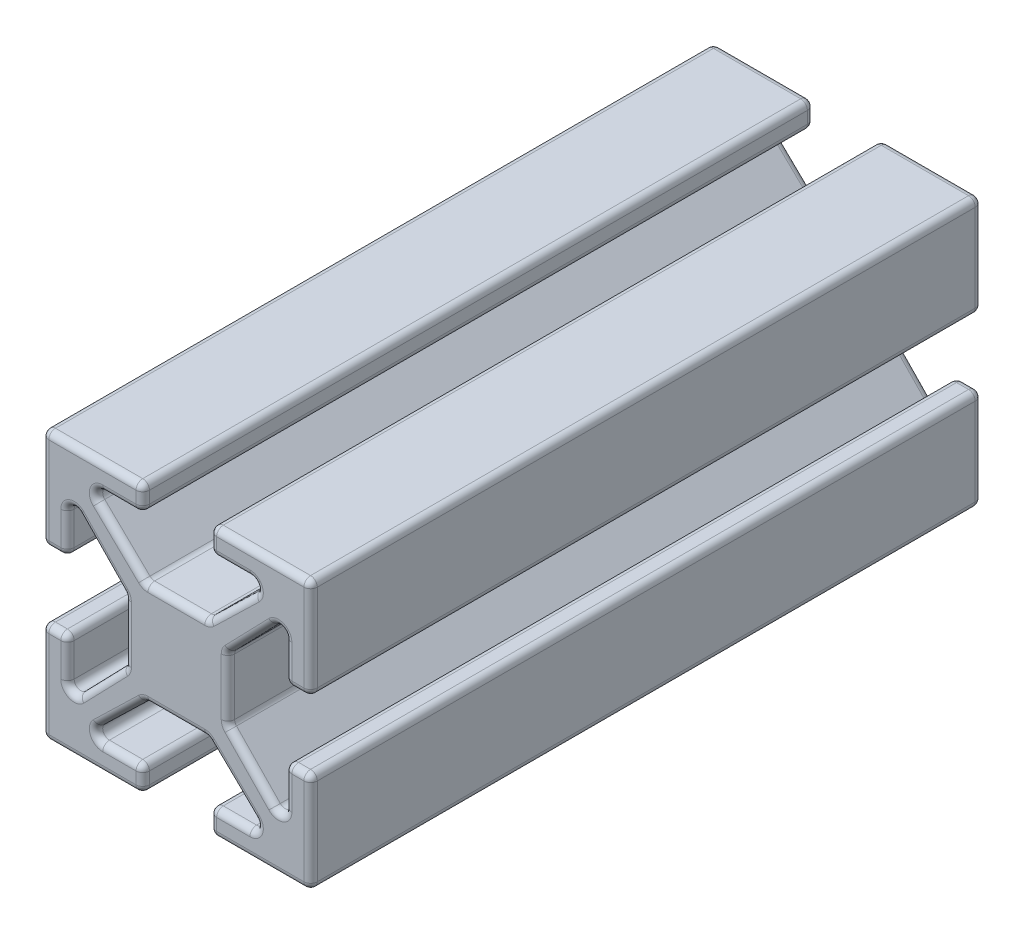
SolidWorks part; units mm, degrees
ref_plane "Front Plane" through (0, 0, 0) normal (0, 0, 1) x (1, 0, 0)
ref_plane "Top Plane" through (0, 0, 0) normal (0, 1, 0) x (1, 0, 0)
ref_plane "Right Plane" through (0, 0, 0) normal (1, 0, 0) x (0, 0, -1)
sketch "Sketch1" plane through (0, 0, 0) normal (0, 0, 1) x (1, 0, 0)
  line L0 (-5, 20) -> (-5, 16.2126)
  line L1 (-20, -20) -> (20, -20)
  line L2 (-20, -20) -> (-20, 20)
  line L3 (-20, 20) -> (20, 20)
  line L4 (20, -20) -> (20, 20)
  line L5 (-20, -20) -> (20, 20) construction
  line L6 (-20, 20) -> (20, -20) construction
  line L7 (-5, 16.2126) -> (-13.4323, 16.2126)
  line L8 (-13.4323, 16.2126) -> (-4.6312, 7.6894)
  line L9 (-4.6312, 7.6894) -> (0, 7.6894)
  line L10 (-7.6894, 4.6312) -> (-7.6894, 0)
  line L11 (-16.2126, 13.4323) -> (-7.6894, 4.6312)
  line L12 (-16.2126, 5) -> (-16.2126, 13.4323)
  line L13 (-20, 5) -> (-16.2126, 5)
  line L14 (0, 7.6894) -> (0, 16.8611) construction
  line L15 (0, 0) -> (-11.384, 0) construction
  line L16 (5, 20) -> (5, 16.2126)
  line L17 (5, 16.2126) -> (13.4323, 16.2126)
  line L18 (13.4323, 16.2126) -> (4.6312, 7.6894)
  line L19 (16.2126, 13.4323) -> (7.6894, 4.6312)
  line L20 (16.2126, 5) -> (16.2126, 13.4323)
  line L21 (20, 5) -> (16.2126, 5)
  line L22 (7.6894, 4.6312) -> (7.6894, 0)
  line L23 (4.6312, 7.6894) -> (0, 7.6894)
  line L24 (20, -5) -> (16.2126, -5)
  line L25 (16.2126, -5) -> (16.2126, -13.4323)
  line L26 (16.2126, -13.4323) -> (7.6894, -4.6312)
  line L27 (13.4323, -16.2126) -> (4.6312, -7.6894)
  line L28 (5, -16.2126) -> (13.4323, -16.2126)
  line L29 (5, -20) -> (5, -16.2126)
  line L30 (4.6312, -7.6894) -> (0, -7.6894)
  line L31 (7.6894, -4.6312) -> (7.6894, 0)
  line L32 (-5, -20) -> (-5, -16.2126)
  line L33 (-5, -16.2126) -> (-13.4323, -16.2126)
  line L34 (-13.4323, -16.2126) -> (-4.6312, -7.6894)
  line L35 (-16.2126, -13.4323) -> (-7.6894, -4.6312)
  line L36 (-16.2126, -5) -> (-16.2126, -13.4323)
  line L37 (-20, -5) -> (-16.2126, -5)
  line L38 (-7.6894, -4.6312) -> (-7.6894, 0)
  line L39 (-4.6312, -7.6894) -> (0, -7.6894)
  point P0 (0, 0)
  point P52 (0, 0)
  dimension "D1" = 40
  dimension "D2" = 40
  dimension "D4" = 15
  dimension "D3" = 4
extrude "Boss-Extrude1" add sketch "Sketch1" along normal blind 100 contours L34 L39 L30 L27 L28 L29 L1 L4 L24 L25 L26 L31 L22 L19 L20 L21 L3 L16 L17 L18 L23 L9 L8 L7 L0 L2 L13 L12 L11 L10 L38 L35 L36 L37 L32 L33 region at (0, 0, 0)
fillet "Fillet3" radius 1 108 edges at (-9.0317, -11.951, 0) (0, -7.6894, 0) (9.0317, -11.951, 0) (9.2161, -16.2126, 0) (5, -18.1063, 0) (12.5, -20, 0) (20, -12.5, 0) (18.1063, -5, 0) (16.2126, -9.2161, 0) (11.951, -9.0317, 0) (7.6894, 0, 0) (11.951, 9.0317, 0) (16.2126, 9.2161, 0) (18.1063, 5, 0) (20, 12.5, 0) (5, 18.1063, 0) (9.2161, 16.2126, 0) (9.0317, 11.951, 0) (0, 7.6894, 0) (-9.0317, 11.951, 0) (-9.2161, 16.2126, 0) (-5, 18.1063, 0) (-12.5, 20, 0) (-20, 12.5, 0) (-18.1063, 5, 0) (-16.2126, 9.2161, 0) (-11.951, 9.0317, 0) (-7.6894, 0, 0) (-11.951, -9.0317, 0) (-16.2126, -9.2161, 0) (-18.1063, -5, 0) (-20, -12.5, 0) (-12.5, -20, 0) (-5, -18.1063, 0) (-9.2161, -16.2126, 0) (-9.0317, -11.951, 100) (0, -7.6894, 100) (9.0317, -11.951, 100) (9.2161, -16.2126, 100) (5, -18.1063, 100) (12.5, -20, 100) (20, -12.5, 100) (18.1063, -5, 100) (16.2126, -9.2161, 100) (11.951, -9.0317, 100) (7.6894, 0, 100) (11.951, 9.0317, 100) (16.2126, 9.2161, 100) (18.1063, 5, 100) (20, 12.5, 100) (12.5, 20, 100) (5, 18.1063, 100) (9.2161, 16.2126, 100) (9.0317, 11.951, 100) (0, 7.6894, 100) (-9.0317, 11.951, 100) (-9.2161, 16.2126, 100) (-5, 18.1063, 100) (-12.5, 20, 100) (-20, 12.5, 100) (-18.1063, 5, 100) (-16.2126, 9.2161, 100) (-11.951, 9.0317, 100) (-7.6894, 0, 100) (-11.951, -9.0317, 100) (-16.2126, -9.2161, 100) (-18.1063, -5, 100) (-20, -12.5, 100) (-12.5, -20, 100) (-5, -18.1063, 100) (-9.2161, -16.2126, 100) (-13.4323, -16.2126, 50) (-5, -16.2126, 50) (-5, -20, 50) (-20, -20, 50) (-20, -5, 50) (-16.2126, -5, 50) (-16.2126, -13.4323, 50) (-7.6894, -4.6312, 50) (-7.6894, 4.6312, 50) (-16.2126, 13.4323, 50) (-16.2126, 5, 50) (-20, 5, 50) (-20, 20, 50) (-5, 20, 50) (-5, 16.2126, 50) (-13.4323, 16.2126, 50) (-4.6312, 7.6894, 50) (4.6312, 7.6894, 50) (13.4323, 16.2126, 50) (5, 16.2126, 50) (5, 20, 50) (20, 20, 50) (20, 5, 50) (16.2126, 5, 50) (16.2126, 13.4323, 50) (7.6894, 4.6312, 50) (7.6894, -4.6312, 50) (16.2126, -13.4323, 50) (16.2126, -5, 50) (20, -5, 50) (20, -20, 50) (5, -20, 50) (5, -16.2126, 50) (13.4323, -16.2126, 50) (4.6312, -7.6894, 50) (-4.6312, -7.6894, 50) (12.5, 20, 0)
ref_plane "Plane1" through (0, 0, 50) normal (0, 0, 1) x (1, 0, 0)
